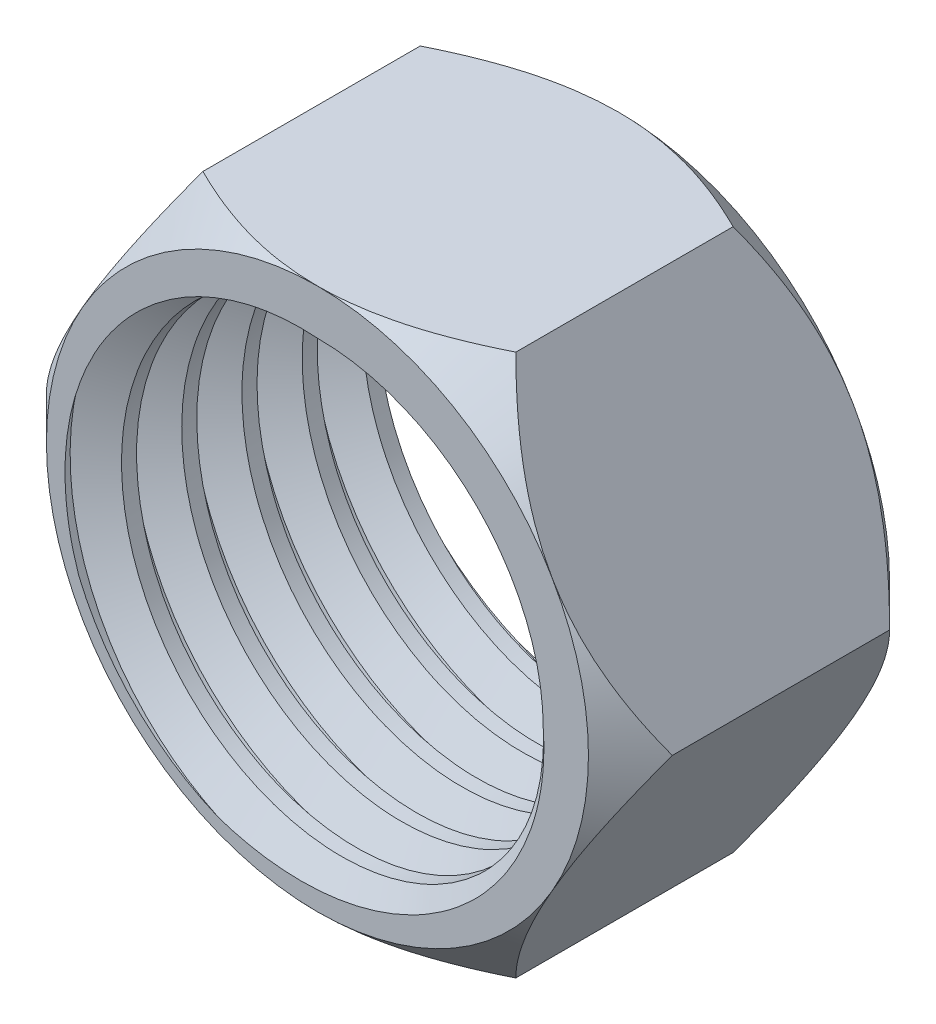
SolidWorks part; units mm, degrees
ref_plane "Front Plane" through (0, 0, 0) normal (0, 0, 1) x (1, 0, 0)
ref_plane "Top Plane" through (0, 0, 0) normal (0, 1, 0) x (1, 0, 0)
ref_plane "Right Plane" through (0, 0, 0) normal (1, 0, 0) x (0, 0, -1)
sketch "Sketch1" plane through (0, 0, 0) normal (0, 0, 1) x (1, 0, 0)
  line L1 (5.1962, 0) -> (2.5981, 4.5)
  line L2 (2.5981, 4.5) -> (-2.5981, 4.5)
  line L3 (-2.5981, 4.5) -> (-5.1962, 0)
  line L4 (-5.1962, 0) -> (-2.5981, -4.5)
  line L5 (-2.5981, -4.5) -> (2.5981, -4.5)
  line L6 (2.5981, -4.5) -> (5.1962, 0)
  circle A0 centre (0, 0) radius 4.5 construction
  point P1 (0, 0)
  dimension "D1" = 9
extrude "Boss-Extrude1" add sketch "Sketch1" along normal blind 7
sketch "Sketch2" plane through (0, 0, 7) normal (0, 0, 1) x (1, 0, 0)
  circle A0 centre (0, 0) radius 4.5
extrude "Cut-Extrude1" cut sketch "Sketch2" against normal blind 5 draft 45 flip side to cut
sketch "Sketch6" plane through (0, 0, 7) normal (0, 0, 1) x (1, 0, 0)
  circle A0 centre (0, 0) radius 3.75
  dimension "D1" = 7.5
extrude "Cut-Extrude3" cut sketch "Sketch6" against normal through all both and the other way through all
thread "Thread2" pitch 1 method cut profile "Thread Profile2" start angle 0, offset 0, length 0, pitch 1, diameter 7.5
ref_plane "Plane3" through (3.75, 0, 0) normal (0, -1, 0) x (1, 0, 0)
sketch "Thread Profile2" plane through (3.75, 0, 0) normal (0, -1, 0) x (1, 0, 0)
  line L0 (0, 0) -> (0, 1) construction
  line L1 (0, 0) -> (0.5413, 0.3125)
  line L2 (0.5413, 0.3125) -> (0.5413, 0.4375)
  line L3 (0.5413, 0.4375) -> (0, 0.75)
  line L4 (0.5413, 0.375) -> (0, 0.375) construction
  line L11 (0, 0) -> (0, 0.75)
  point P2 (0, 0)
  dimension "Pitch" = 1
  dimension "Profile_Angle" = 60
  dimension "Profile_Land" = 0.125
  dimension "Profile_Height" = 0.5413
sketch "Sketch9" plane through (0, 0, 0) normal (0, 0, -1) x (-1, 0, 0)
  line L6 (-5.1962, 0) -> (-2.5981, -4.5)
  line L7 (-2.5981, -4.5) -> (2.5981, -4.5)
  line L8 (2.5981, -4.5) -> (5.1962, 0)
  line L9 (5.1962, 0) -> (2.5981, 4.5)
  line L10 (2.5981, 4.5) -> (-2.5981, 4.5)
  line L11 (-2.5981, 4.5) -> (-5.1962, 0)
  line L12 (-5.1962, 0) -> (-2.5981, -4.5)
  line L13 (-2.5981, -4.5) -> (2.5981, -4.5)
  line L14 (2.5981, -4.5) -> (5.1962, 0)
  line L15 (5.1962, 0) -> (2.5981, 4.5)
  line L16 (2.5981, 4.5) -> (-2.5981, 4.5)
  line L17 (-2.5981, 4.5) -> (-5.1962, 0)
  dimension "D1" = 0
extrude "Cut-Extrude4" cut sketch "Sketch9" against normal blind 2 and the other way through all
ref_plane "Plane4" through (0, 0, 4.5) normal (0, 0, -1) x (-1, 0, 0)
mirror "Mirror2" about plane through (0, 0, 4.5) normal (0, 0, -1) of "Cut-Extrude1"
